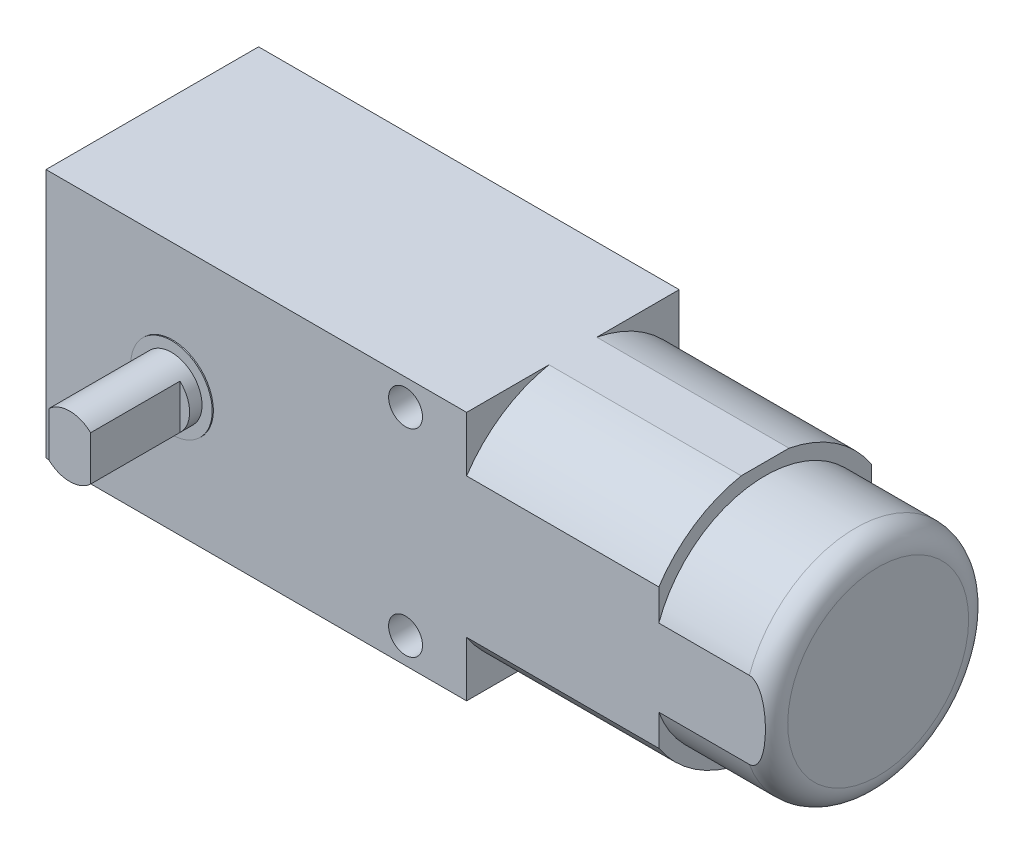
SolidWorks part; units mm, degrees
ref_plane "前视基准面" through (0, 0, 0) normal (0, 0, 1) x (1, 0, 0)
ref_plane "上视基准面" through (0, 0, 0) normal (0, 1, 0) x (1, 0, 0)
ref_plane "右视基准面" through (0, 0, 0) normal (1, 0, 0) x (0, 0, -1)
sketch "草图2" plane through (0, 0, 0) normal (1, 0, 0) x (0, 0, -1)
  line L1 (-9.4, -11.05) -> (9.4, -11.05)
  line L2 (-9.4, -11.05) -> (-9.4, 11.05)
  line L3 (-9.4, 11.05) -> (9.4, 11.05)
  line L4 (9.4, -11.05) -> (9.4, 11.05)
  line L5 (-9.4, -11.05) -> (9.4, 11.05) construction
  line L6 (-9.4, 11.05) -> (9.4, -11.05) construction
  point P0 (0, 0)
  dimension "D1" = 18.8
  dimension "D2" = 22.1
extrude "凸台-拉伸1" add sketch "草图2" along normal blind 64.2
sketch "草图4" plane through (0, 0, 9.4) normal (0, 0, 1) x (1, 0, 0)
  line L0 (0, 11.05) -> (0, -11.05) construction
  circle A0 centre (11.2, 0) radius 3.6
  dimension "D1" = 7.2
  dimension "D2" = 11.2
extrude "凸台-拉伸2" add sketch "草图4" along normal blind 0.1
sketch "草图5" plane through (0, 0, 9.4) normal (0, 0, 1) x (1, 0, 0)
  circle A0 centre (11.2, 0) radius 2.7
  dimension "D1" = 5.4
extrude "凸台-拉伸3" add sketch "草图5" along normal offset from surface (9.1 mm away) 9.1 up to face at (7.6, 0, 9.4) offset beyond the face yes
sketch "草图6" plane through (0, 0, 18.5) normal (0, 0, 1) x (1, 0, 0)
  line L0 (9.35, 1.9666) -> (9.35, -1.9666)
  line L1 (11.2, -1000) -> (11.2, 49000) construction
  line L2 (13.05, 1.9666) -> (13.05, -1.9666)
  circle A1 centre (11.2, 0) radius 2.7
  circle A2 centre (11.2, 0) radius 2.7
  circle M4 centre (11.2, 0) radius 2.7
  dimension "D2" = 3.7
  dimension "D1" = 0
extrude "切除-拉伸1" cut sketch "草图6" against normal blind 7.9 contours L0 M4 | L2 M4 region at (9.0049, 0, 18.5) region at (13.3951, 0, 18.5)
sketch "草图7" plane through (64.2, 0, 0) normal (1, 0, 0) x (0, 0, -1)
  line L4 (9.4, -11.05) -> (9.4, 11.05)
  line L5 (9.4, 11.05) -> (-9.4, 11.05)
  line L6 (-9.4, 11.05) -> (-9.4, -11.05)
  line L7 (-9.4, -11.05) -> (9.4, -11.05)
  line L8 (9.4, -11.05) -> (9.4, 11.05)
  line L9 (9.4, 11.05) -> (-9.4, 11.05)
  line L10 (-9.4, 11.05) -> (-9.4, -11.05)
  line L11 (-9.4, -11.05) -> (9.4, -11.05)
  circle A1 centre (0, 0) radius 11.25
  line M6 (9.4, -11.05) -> (9.4, 11.05)
  line M7 (9.4, 11.05) -> (-9.4, 11.05)
  line M8 (-9.4, 11.05) -> (-9.4, -11.05)
  line M9 (-9.4, -11.05) -> (9.4, -11.05)
  dimension "D2" = 22.5
  dimension "D1" = 0
extrude "切除-拉伸2" cut sketch "草图7" against normal blind 27 contours A1 M7 M8 | A1 M6 M7 | A1 M9 M6 | A1 M8 M9 region at (64.2, -9.6425, -7.3961) region at (64.2, 9.6425, -7.3961) region at (64.2, -9.6425, 7.3961) region at (64.2, 9.6425, 7.3961)
sketch "草图9" plane through (64.2, 0, 0) normal (1, 0, 0) x (0, 0, -1)
  line L4 (-2.1119, -11.05) -> (2.1119, -11.05)
  line L5 (9.4, -6.1808) -> (9.4, 6.1808)
  line L6 (2.1119, 11.05) -> (-2.1119, 11.05)
  line L7 (-9.4, 6.1808) -> (-9.4, -6.1808)
  line L8 (-2.1119, -11.05) -> (2.1119, -11.05)
  line L9 (9.4, -6.1808) -> (9.4, 6.1808)
  line L10 (2.1119, 11.05) -> (-2.1119, 11.05)
  line L11 (-9.4, 6.1808) -> (-9.4, -6.1808)
  circle A0 centre (0, 0) radius 10
  arc A5 (-9.4, -6.1808) -> (-2.1119, -11.05) centre (0, 0) ccw
  arc A6 (2.1119, -11.05) -> (9.4, -6.1808) centre (0, 0) ccw
  arc A7 (9.4, 6.1808) -> (2.1119, 11.05) centre (0, 0) ccw
  arc A8 (-2.1119, 11.05) -> (-9.4, 6.1808) centre (0, 0) ccw
  arc A9 (-9.4, -6.1808) -> (-2.1119, -11.05) centre (0, 0) ccw
  arc A10 (2.1119, -11.05) -> (9.4, -6.1808) centre (0, 0) ccw
  arc A11 (9.4, 6.1808) -> (2.1119, 11.05) centre (0, 0) ccw
  arc A12 (-2.1119, 11.05) -> (-9.4, 6.1808) centre (0, 0) ccw
  arc M9 (-9.4, -6.1808) -> (-2.1119, -11.05) centre (0, 0) ccw
  line M10 (-2.1119, -11.05) -> (2.1119, -11.05)
  arc M11 (2.1119, -11.05) -> (9.4, -6.1808) centre (0, 0) ccw
  line M12 (9.4, -6.1808) -> (9.4, 6.1808)
  arc M13 (9.4, 6.1808) -> (2.1119, 11.05) centre (0, 0) ccw
  line M14 (2.1119, 11.05) -> (-2.1119, 11.05)
  arc M15 (-2.1119, 11.05) -> (-9.4, 6.1808) centre (0, 0) ccw
  line M16 (-9.4, 6.1808) -> (-9.4, -6.1808)
  dimension "D1" = 20
  dimension "D2" = 0
extrude "切除-拉伸3" cut sketch "草图9" against normal blind 10 contours A0 M12 M13 M14 M15 M16 | A0 M16 M9 M10 M11 M12 region at (64.2, -9.1857, 6.1369) region at (64.2, 4.7963, 9.1971)
fillet "圆角1" radius 2 1 edges at (64.2, 10, 0)
sketch "草图10" plane through (0, 0, 9.4) normal (0, 0, 1) x (1, 0, 0)
  line L0 (-988.8, 0) -> (49011.2, 0) construction
  line L1 (0, 11.05) -> (0, -11.05) construction
  circle A0 centre (31.8, 8.75) radius 1.5
  circle A1 centre (31.8, -8.75) radius 1.5
  dimension "D1" = 3
  dimension "D2" = 17.5
  dimension "D3" = 31.8
extrude "切除-拉伸4" cut sketch "草图10" against normal blind 3
